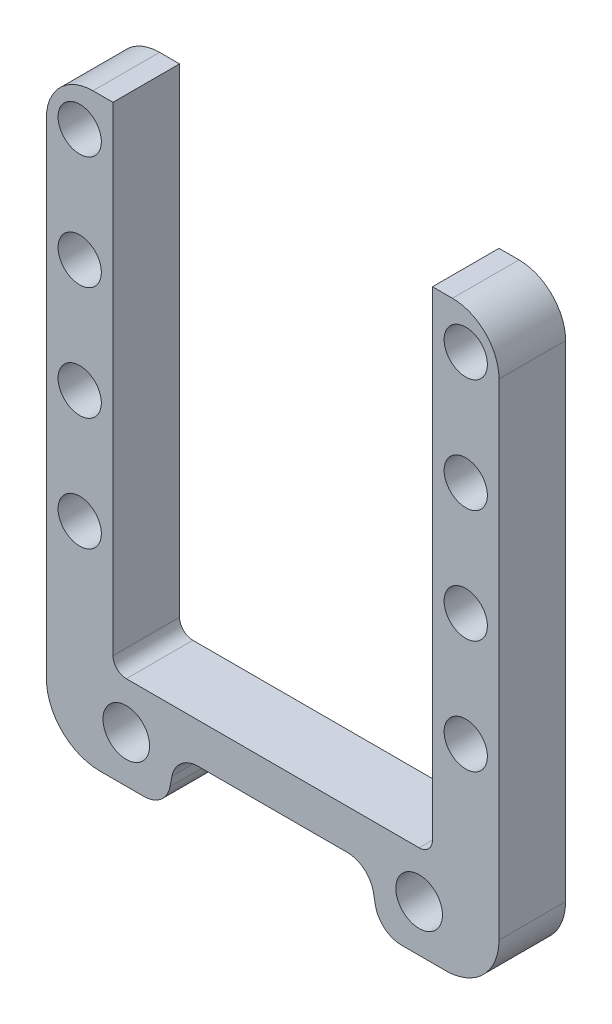
SolidWorks part; units mm, degrees
ref_plane "Plan de face" through (0, 0, 0) normal (0, 0, 1) x (1, 0, 0)
ref_plane "Plan de dessus" through (0, 0, 0) normal (0, 1, 0) x (1, 0, 0)
ref_plane "Plan de droite" through (0, 0, 0) normal (1, 0, 0) x (0, 0, -1)
sketch "Esquisse1" plane through (0, 0, 0) normal (0, 0, 1) x (1, 0, 0)
  line L0 (24, 104) -> (24, 30)
  line L1 (24, 30) -> (0, 30)
  line L7 (0, 24) -> (14.5, 24)
  line L8 (14.5, 24) -> (16.055, 16)
  line L9 (16.055, 16) -> (34, 16)
  line L10 (34, 16) -> (34, 104)
  line L11 (34, 104) -> (24, 104)
  line L12 (0, 30) -> (0, 24)
  line L13 (0, -0.15) -> (0, 72.4519) construction
  circle A0 centre (29, 98) radius 3.25
  circle A1 centre (22, 23) radius 3.5
  circle A2 centre (29, 81) radius 3.25
  circle A3 centre (29, 64) radius 3.25
  circle A4 centre (29, 47) radius 3.25
  point P19 (29, 104)
  dimension "D9" = 7
  dimension "D10" = 6
  dimension "D14" = 6.5
  dimension "D1" = 6
  dimension "D2" = 24
  dimension "D3" = 101
  dimension "D4" = 24
  dimension "D5" = 10
  dimension "D6" = 74
  dimension "D7" = 8
  dimension "D8" = 14.5
  dimension "D11" = 34
  dimension "D12" = 1
  dimension "D13" = 22
  dimension "D15" = 34
  dimension "D16" = 17
extrude "Boss.-Extru.1" add sketch "Esquisse1" along normal blind 10
mirror "Symétrie2" about plane through (0, 30, 10) normal (1, 0, 0) of "Boss.-Extru.1"
fillet "Congé1" radius 4 4 edges at (16.055, 16, 5) (-16.055, 16, 5) (-14.5, 24, 5) (14.5, 24, 5)
fillet "Congé2" radius 8 2 edges at (-34, 16, 5) (34, 16, 5)
fillet "Congé3" radius 7 2 edges at (34, 104, 5) (-34, 104, 5)
fillet "Congé4" radius 2 2 edges at (-24, 30, 5) (24, 30, 5)
sketch "Esquisse2" plane through (0, 0, 0) normal (0, 0, 1) x (1, 0, 0)
  line L1 (-43.837, 32.6956) -> (53.3136, 32.6956)
  line L2 (-43.837, 32.6956) -> (-43.837, 118.0236)
  line L3 (-43.837, 118.0236) -> (53.3136, 118.0236)
  line L4 (53.3136, 32.6956) -> (53.3136, 118.0236)
